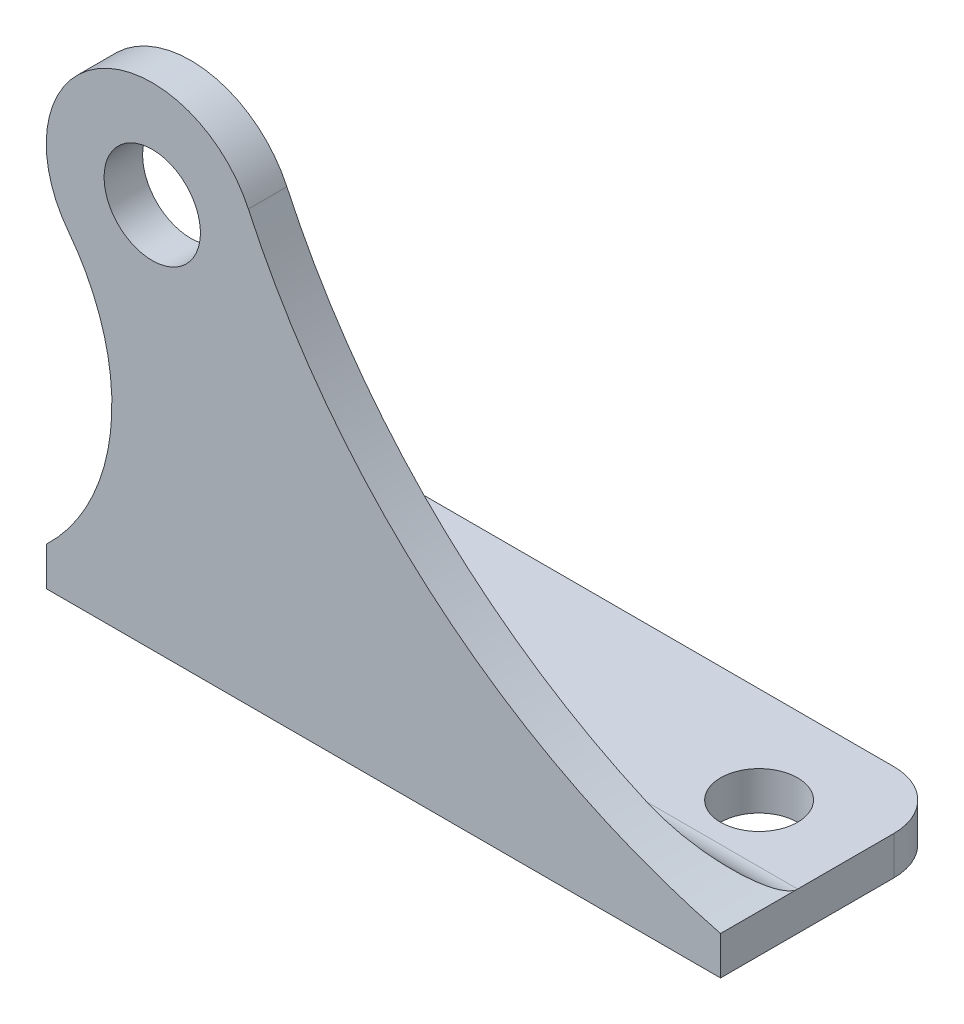
SolidWorks part; units mm, degrees
ref_plane "Front Plane" through (0, 0, 0) normal (0, 0, 1) x (1, 0, 0)
ref_plane "Top Plane" through (0, 0, 0) normal (0, 1, 0) x (1, 0, 0)
ref_plane "Right Plane" through (0, 0, 0) normal (1, 0, 0) x (0, 0, -1)
sketch "Sketch1" plane through (0, 0, 0) normal (0, 0, 1) x (1, 0, 0)
  line L0 (0, 34.5512) -> (0, -21.8179) construction
  line L1 (-25.489, 0) -> (33.3088, 0) construction
  line L2 (-5.5, 0) -> (-5.5, 2)
  line L4 (29.5, 2) -> (29.5, 0)
  line L5 (29.5, 0) -> (-5.5, 0)
  circle A0 centre (0, 20) radius 2.5
  arc A1 (4.9899, 22.3131) -> (-4.3644, 16.653) centre (0, 20) ccw
  arc A2 (4.9899, 22.3131) -> (29.5, 2) centre (38.5587, 37.874) ccw
  arc A3 (-4.3644, 16.653) -> (-5.5, 2) centre (-13.0931, 9.959) cw
  point P8 (0, 0)
  dimension "D1" = 5
  dimension "D3" = 3
  dimension "D6" = 37
  dimension "D7" = 11
  dimension "D2" = 20
  dimension "D4" = 2
  dimension "D5" = 35
extrude "Boss-Extrude1" add sketch "Sketch1" along normal blind 2
sketch "Sketch2" plane through (0, 0, 2) normal (0, 0, 1) x (1, 0, 0)
  line L1 (-5.5, 0) -> (29.5, 0)
  line L2 (-5.5, 0) -> (-5.5, 2)
  line L3 (-5.5, 2) -> (29.5, 2)
  line L4 (29.5, 0) -> (29.5, 2)
extrude "Boss-Extrude2" add sketch "Sketch2" along normal blind 10
sketch "Sketch3" plane through (0, 2, 0) normal (0, 1, 0) x (1, 0, 0)
  line L0 (-10.6996, -7) -> (35.8591, -7) construction
  line L1 (-5.5, -12) -> (-5.5, -2) construction
  line L2 (29.5, -12) -> (29.5, -2) construction
  line L3 (29.5, -12) -> (-5.5, -12) construction
  circle A0 centre (-0.5, -7) radius 2
  circle A1 centre (24.5, -7) radius 2
  dimension "D1" = 4
  dimension "D2" = 4
  dimension "D3" = 5
  dimension "D4" = 5
  dimension "D5" = 5
extrude "Cut-Extrude1" cut sketch "Sketch3" against normal through all
fillet "Fillet1" radius 2 1 edges at (12, 2, 2)
fillet "Fillet2" radius 3 2 edges at (-5.5, 1, 12) (29.5, 1, 12)
mirror "Mirror1" about plane through (-13.0931, 9.959, 0) normal (0, 0, -1) of "Fillet2", "Fillet1", "Cut-Extrude1", "Boss-Extrude1", "Boss-Extrude2"
sketch "Sketch4" plane through (0, 0, 0) normal (1, 0, 0) x (0, 0, -1)
  line L1 (0, 0) -> (-15.9901, 0)
  line L2 (0, 0) -> (0, 26.8223)
  line L3 (0, 26.8223) -> (-15.9901, 26.8223)
  line L4 (-15.9901, 0) -> (-15.9901, 26.8223)
extrude "Cut-Extrude2" cut sketch "Sketch4" against normal through all both and the other way through all
